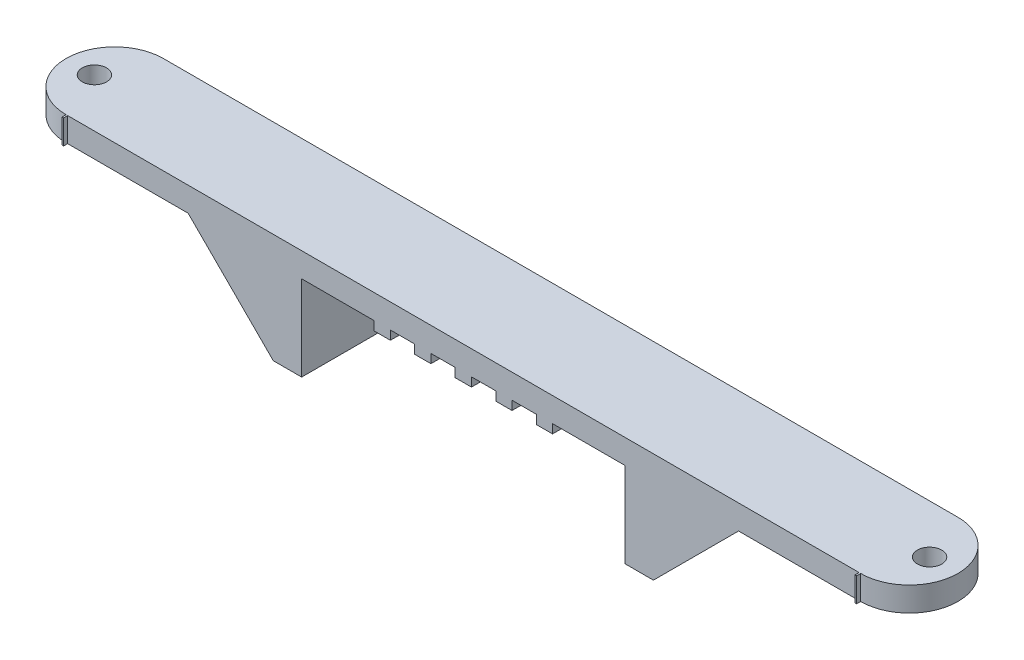
SolidWorks part; units mm, degrees
ref_plane "Front Plane" through (0, 0, 0) normal (0, 0, 1) x (1, 0, 0)
ref_plane "Top Plane" through (0, 0, 0) normal (0, 1, 0) x (1, 0, 0)
ref_plane "Right Plane" through (0, 0, 0) normal (1, 0, 0) x (0, 0, -1)
sketch "Sketch1" plane through (0, 0, 0) normal (0, 1, 0) x (1, 0, 0)
  line L0 (-49, 0) -> (49, 0) construction
  line L1 (-49, 6) -> (49, 6)
  line L2 (-49, -6) -> (49, -6)
  arc A0 (-49, 6) -> (-49, -6) centre (-49, 0) ccw
  arc A1 (49, -6) -> (49, 6) centre (49, 0) ccw
  circle A2 centre (-51.5, 0) radius 1.5
  circle A3 centre (51.5, 0) radius 1.5
  point P2 (0, 0)
  point P12 (-55, 0)
  point P13 (55, 0)
  dimension "D3" = 3
  dimension "D4" = 3.5
  dimension "D1" = 110
  dimension "D2" = 12
  dimension "D5" = 3.5
extrude "Boss-Extrude1" add sketch "Sketch1" along normal blind 3 contours L2 A1 L1 A0 | A2 | A3
sketch "Sketch4" plane through (0, 0, 0) normal (0, -1, 0) x (1, 0, 0)
  line L0 (-19.94, 6) -> (-19.94, -6)
  line L1 (-49, 6) -> (49, 6) construction
  line L2 (-49, -6) -> (49, -6) construction
  line L3 (-19.94, -6) -> (-23.44, -6)
  line L4 (-23.44, -6) -> (-23.44, 6)
  line L5 (-23.44, 6) -> (-19.94, 6)
  line L6 (0, 6) -> (0, -6) construction
  line L7 (-19.94, 5.075) -> (-19.94, -14.3256) construction
  line L8 (23.44, -6) -> (23.44, 6)
  line L9 (19.94, -6) -> (23.44, -6)
  line L10 (19.94, 6) -> (19.94, -6)
  line L11 (23.44, 6) -> (19.94, 6)
  dimension "D1" = 0
  dimension "D2" = 3.5
extrude "Boss-Extrude3" add sketch "Sketch4" along normal blind 10.5
sketch "Sketch5" plane through (0, 0, 0) normal (0, -1, 0) x (1, 0, 0)
  line L1 (4, 6) -> (4, -6)
  line L2 (4, 6) -> (6, 6)
  line L6 (-19.94, -6) -> (19.94, -6) construction
  line L7 (-1, 6) -> (1, 6)
  line L8 (-1, 6) -> (-1, -6)
  line L9 (-1, -6) -> (1, -6)
  line L10 (1, 6) -> (1, -6)
  line L11 (-1, 6) -> (1, -6) construction
  line L12 (-1, -6) -> (1, 6) construction
  line L13 (6, 6) -> (6, -6)
  line L14 (4, -6) -> (6, -6)
  line L15 (9, 6) -> (9, -6)
  line L16 (9, 6) -> (11, 6)
  line L17 (11, 6) -> (11, -6)
  line L18 (9, -6) -> (11, -6)
  line L19 (-4, 6) -> (-4, -6)
  line L20 (-6, -6) -> (-4, -6)
  line L21 (-6, 6) -> (-6, -6)
  line L22 (-6, 6) -> (-4, 6)
  line L23 (-9, 6) -> (-9, -6)
  line L24 (-11, -6) -> (-9, -6)
  line L25 (-11, 6) -> (-11, -6)
  line L26 (-11, 6) -> (-9, 6)
  point P0 (0, 0)
  dimension "D1" = 2
  dimension "D2" = 3
  dimension "D3" = 3
extrude "Boss-Extrude4" add sketch "Sketch5" along normal blind 1.1
sketch "Sketch6" plane through (0, 0, 6) normal (0, 0, 1) x (1, 0, 0)
  line L0 (49, 0) -> (49, 3)
  line L1 (49, 3) -> (48.8, 3)
  line L2 (-49, 3) -> (49, 3) construction
  line L3 (48.8, 3) -> (48.8, 0)
  line L4 (23.44, 0) -> (49, 0) construction
  line L5 (48.8, 0) -> (49, 0)
  line L6 (0, 0) -> (0, 3) construction
  line L7 (-48.8, 0) -> (-49, 0)
  line L8 (-48.8, 3) -> (-48.8, 0)
  line L9 (-49, 3) -> (-48.8, 3)
  line L10 (-49, 0) -> (-49, 3)
  dimension "D1" = 0.2
extrude "Boss-Extrude5" add sketch "Sketch6" along normal blind 0.5 contours L0 L1 L3 L5 | L8 L7 L10 L9
chamfer "Chamfer1" distance 10.5 2 edges at (23.44, 0, 0) (-23.44, 0, 0)
hole_wizard "Ø3.0mm Dowel Hole1" positions "Sketch7" profile "Sketch9" hole size "Ø3.0" standard "ANSI Metric" end condition up to next
sketch "Sketch7" plane through (0, 3, 0) normal (0, 1, 0) x (1, 0, 0)
  point P0 (-51.5, 0)
  point P2 (51.5, 0)
sketch "Sketch9" plane through (-51.5, 3, 0) normal (1, 0, 0) x (0, 0, 1)
  line L0 (0, 0) -> (0, 13.5)
  line L1 (0, 13.5) -> (1.5, 13.5)
  line L2 (1.5, 13.5) -> (1.5, 0)
  line L5 (1.5, 0) -> (0, 0)
  line L11 (0, -6.35) -> (0, 107.95) construction
  dimension "Thru Hole Dia." = 3
  dimension "Thru Hole Depth" = 13.5
